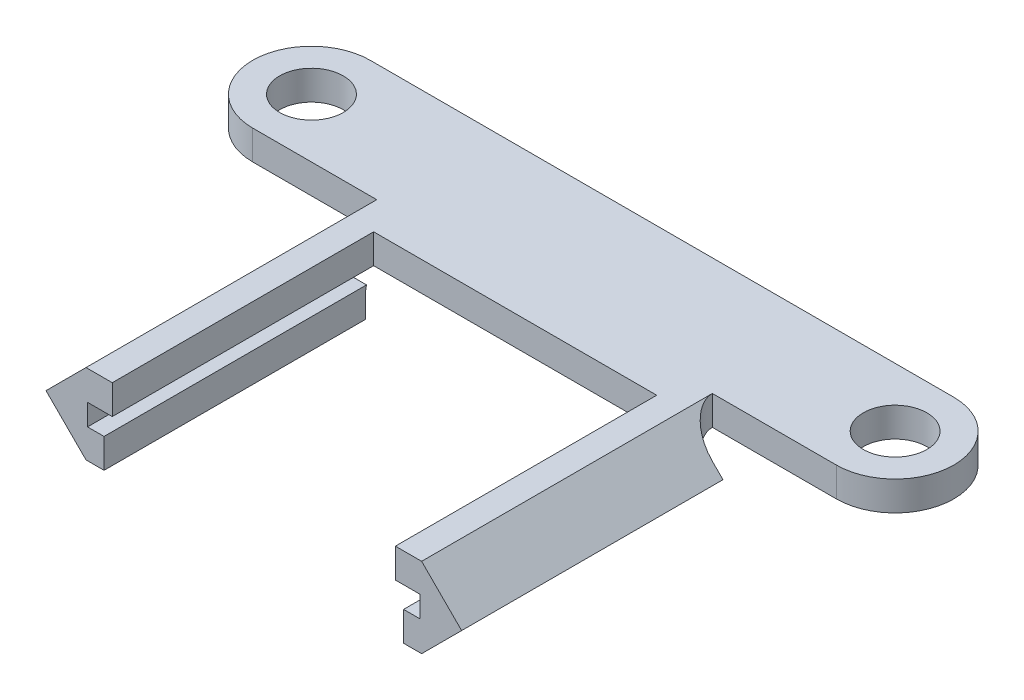
SolidWorks part; units mm, degrees
ref_plane "Front Plane" through (0, 0, 0) normal (0, 0, 1) x (1, 0, 0)
ref_plane "Top Plane" through (0, 0, 0) normal (0, 1, 0) x (1, 0, 0)
ref_plane "Right Plane" through (0, 0, 0) normal (1, 0, 0) x (0, 0, -1)
sketch "Sketch1" plane through (0, 0, 0) normal (0, 0, 1) x (1, 0, 0)
  line L0 (0.8255, 1.8415) -> (0, 1.8415)
  line L1 (0, 0) -> (0.8255, 0) construction
  line L2 (0, 0) -> (0, 1.8415) construction
  line L3 (0, 1.8415) -> (0.8255, 1.8415) construction
  line L4 (0.8255, 0) -> (0.8255, 1.8415) construction
  line L5 (0.4127, 1.8415) -> (0.4128, 0) construction
  line L6 (0, 0.9207) -> (0.8255, 0.9207) construction
  line L7 (0.8255, 0) -> (0, 0)
  line L8 (0, 0) -> (-0.9208, 0.9208) construction
  line L9 (-0.9208, 0.9208) -> (0, 1.8415) construction
  line L10 (26.0985, 0) -> (26.924, 0)
  line L11 (0.8255, 1.8415) -> (26.0985, 1.8415)
  line L12 (0.8255, 1.8415) -> (0.8255, 0) construction
  line L13 (0.8255, 0) -> (26.0985, 0)
  line L14 (26.0985, 1.8415) -> (26.0985, 0) construction
  line L15 (13.462, 0) -> (13.462, 1.8415) construction
  line L16 (0.8255, 0.9207) -> (26.0985, 0.9207) construction
  line L17 (26.924, 0) -> (27.8448, 0.9208) construction
  line L18 (26.0985, 1.8415) -> (26.924, 1.8415)
  line L19 (27.8448, 0.9208) -> (26.924, 1.8415) construction
  line L20 (-4.5129, 0.9207) -> (-1.0521, 4.3815)
  line L21 (0.8255, 4.3815) -> (-1.0521, 4.3815)
  line L22 (0.8255, 4.3815) -> (26.0985, 4.3815)
  line L23 (26.0985, 4.3815) -> (27.9761, 4.3815)
  line L24 (31.4369, 0.9207) -> (27.9761, 4.3815)
  line L25 (27.9761, -2.54) -> (31.4369, 0.9207)
  line L26 (26.0985, -2.54) -> (27.9761, -2.54)
  line L27 (0.8255, -2.54) -> (26.0985, -2.54)
  line L28 (0.8255, -2.54) -> (-1.0521, -2.54)
  line L29 (-1.0521, -2.54) -> (-4.5129, 0.9207)
  line L30 (0, 1.8415) -> (-0.9208, 1.8415)
  line L31 (-0.9208, 1.8415) -> (-0.9208, 0)
  line L32 (-0.9208, 0) -> (0, 0)
  line L33 (26.924, 1.8415) -> (27.8448, 1.8415)
  line L34 (27.8448, 1.8415) -> (27.8448, 0)
  line L35 (27.8448, 0) -> (26.924, 0)
  point P287 (13.462, 0.9207)
  point P500 (0.4127, 0.9207)
  dimension "D1" = 1.8415
  dimension "D2" = 0.8255
  dimension "D3" = 45
  dimension "D4" = 25.273
  dimension "D5" = 2.54
extrude "Boss-Extrude1" add sketch "Sketch1" along normal blind 22.606
sketch "Sketch2" plane through (0, 0, 22.606) normal (0, 0, 1) x (1, 0, 0)
  line L5 (13.462, 0) -> (13.462, -2.54) construction
  line L6 (-0.9208, 0) -> (27.8448, 0) construction
  line L7 (-1.0521, -2.54) -> (27.9761, -2.54) construction
  line L9 (0.508, 0) -> (26.416, 0)
  line L10 (0.508, 0) -> (0.508, -2.54)
  line L11 (0.508, -2.54) -> (26.416, -2.54)
  line L12 (26.416, 0) -> (26.416, -2.54)
  line L13 (13.462, -2.54) -> (13.462, 0) construction
  line L14 (0.508, -1.27) -> (26.416, -1.27) construction
  point P218 (13.462, -1.27)
  dimension "D1" = 0.508
extrude "Cut-Extrude1" cut sketch "Sketch2" against normal blind 22.606
sketch "Sketch5" plane through (0, 0, 0) normal (0, 0, -1) x (-1, 0, 0)
  line L12 (-31.4369, 0.9207) -> (-27.8448, 0.9208)
  line L13 (-27.8448, 0.9208) -> (-27.8448, 1.8415)
  line L14 (-27.8448, 1.8415) -> (0.9208, 1.8415)
  line L15 (0.9208, 1.8415) -> (0.9208, 0.9207)
  line L16 (0.9208, 1.8415) -> (0.9208, 0) construction
  line L17 (0.9208, 0.9207) -> (4.5129, 0.9207)
  line L18 (4.5129, 0.9207) -> (1.0521, 4.3815)
  line L19 (1.0521, 4.3815) -> (-27.9761, 4.3815)
  line L20 (-27.9761, 4.3815) -> (-31.4369, 0.9207)
extrude "Boss-Extrude2" add sketch "Sketch5" along normal blind 12.7
sketch "Sketch3" plane through (0, 4.3815, 0) normal (0, 1, 0) x (1, 0, 0)
  line L0 (13.462, 0) -> (13.462, -22.606) construction
  line L1 (27.9761, 0) -> (-1.0521, 0) construction
  line L2 (27.9761, -22.606) -> (-1.0521, -22.606) construction
  line L3 (6.1658, -15.0622) -> (3.048, -15.0622) construction
  line L4 (1.2192, 0) -> (25.7048, 0) construction
  line L5 (1.2192, 0) -> (1.2192, -22.606) construction
  line L6 (1.2192, -22.606) -> (25.7048, -22.606) construction
  line L7 (25.7048, 0) -> (25.7048, -22.606) construction
  line L8 (13.462, -22.606) -> (13.462, 0) construction
  line L9 (1.2192, -11.303) -> (25.7048, -11.303) construction
  line L10 (6.1658, 0) -> (20.7582, 0) construction
  line L11 (6.1658, 0) -> (6.1658, -15.0622) construction
  line L12 (6.1658, -15.0622) -> (20.7582, -15.0622) construction
  line L13 (20.7582, 0) -> (20.7582, -15.0622) construction
  line L14 (13.462, -15.0622) -> (13.462, 0) construction
  line L15 (6.1658, -7.5311) -> (20.7582, -7.5311) construction
  line L16 (3.048, 0) -> (23.876, 0) construction
  line L17 (3.048, 0) -> (3.048, -22.606) construction
  line L18 (3.048, -22.606) -> (23.876, -22.606) construction
  line L19 (23.876, 0) -> (23.876, -22.606) construction
  line L20 (13.462, -22.606) -> (13.462, 0) construction
  line L21 (3.048, -11.303) -> (23.876, -11.303) construction
  line L22 (3.048, -15.0622) -> (3.048, 0) construction
  line L23 (3.048, 0) -> (1.2192, 0)
  line L24 (1.2192, 0) -> (1.2192, -22.606)
  line L25 (1.2192, -22.606) -> (25.7048, -22.606)
  line L26 (25.7048, -22.606) -> (25.7048, 0)
  line L27 (25.7048, 0) -> (23.876, 0)
  line L28 (23.876, 0) -> (23.876, -15.0622) construction
  line L29 (23.876, -15.0622) -> (20.7582, -15.0622) construction
  line L32 (6.1658, 0) -> (20.7582, 0)
  line L33 (3.048, 0) -> (6.1658, 0)
  line L34 (20.7582, 0) -> (23.876, 0)
  point P250 (13.462, -11.303)
  point P383 (13.462, -7.5311)
  point P386 (13.462, -11.303)
  dimension "D1" = 24.4856
  dimension "D2" = 14.5923
  dimension "D3" = 15.0622
  dimension "D4" = 20.828
extrude "Cut-Extrude4" cut sketch "Sketch3" against normal up to vertex (2.54 mm away)
sketch "Sketch6" plane through (0, 0, -12.7) normal (0, 0, -1) x (-1, 0, 0)
  line L2 (-27.9761, 4.3815) -> (-31.4369, 0.9207)
  line L3 (-31.4369, 0.9207) -> (-27.8448, 0.9208)
  line L4 (-27.8448, 0.9208) -> (-27.8448, 1.8415)
  line L5 (-27.8448, 1.8415) -> (-27.9761, 1.8415)
  line L6 (-27.9761, 1.8415) -> (-27.9761, 4.3815)
  line L8 (-13.462, 4.3815) -> (-13.462, 1.8415) construction
  line L9 (-0.8255, 4.3815) -> (-26.0985, 4.3815) construction
  line L11 (1.0521, 1.8415) -> (1.0521, 4.3815)
  line L12 (0.9208, 1.8415) -> (1.0521, 1.8415)
  line L13 (0.9208, 0.9208) -> (0.9208, 1.8415)
  line L14 (4.5129, 0.9208) -> (0.9208, 0.9208)
  line L15 (1.0521, 4.3815) -> (4.5129, 0.9208)
extrude "Cut-Extrude5" cut sketch "Sketch6" against normal up to surface (12.7 mm away) up to face at (-1.0651, -0.5398, 0)
fillet "Fillet1" radius 2.54 8 edges at (27.9761, 3.1115, 0) (27.9104, 1.8415, 0) (-0.9864, 1.8415, 0) (-1.0521, 3.1115, 0) (-0.2064, 0, 0) (27.8448, 0.9207, 0) (27.1304, 0, 0) (-0.9208, 0.9208, 0)
sketch "Sketch7" plane through (0, 1.8415, 0) normal (0, -1, 0) x (1, 0, 0)
  line L2 (13.462, 0) -> (13.462, -12.7) construction
  line L3 (25.7048, 0) -> (1.2192, 0) construction
  line L4 (27.9761, -12.7) -> (-1.0521, -12.7) construction
  line L5 (-1.0521, -7.62) -> (27.9761, -7.62) construction
  line L6 (-1.0521, -2.54) -> (-1.0521, -12.7) construction
  line L7 (27.9761, -2.54) -> (27.9761, -12.7) construction
  line L8 (-1.0521, -7.62) -> (-11.778, -7.62) construction
  line L9 (-1.0521, -2.54) -> (-11.778, -2.54)
  line L10 (-1.0521, -2.54) -> (27.9761, -2.54)
  line L11 (27.9761, -2.54) -> (38.702, -2.54)
  line L12 (27.9761, -12.7) -> (38.702, -12.7)
  line L13 (-1.0521, -12.7) -> (27.9761, -12.7)
  line L14 (-1.0521, -12.7) -> (-11.778, -12.7)
  line L15 (-11.778, -2.54) -> (-11.778, -12.7) construction
  circle A4 centre (-11.778, -7.62) radius 2 construction
  circle A5 centre (38.702, -7.62) radius 2 construction
  arc A6 (-11.778, -12.7) -> (-11.778, -2.54) centre (-11.778, -7.62) cw
  arc A7 (38.702, -12.7) -> (38.702, -2.54) centre (38.702, -7.62) ccw
  dimension "D1" = 50.48
  dimension "D2" = 4
extrude "Boss-Extrude3" add sketch "Sketch7" against normal up to surface (2.54 mm away) up to face at (13.462, 4.3815, 5.9944)
hole_wizard "M5 Clearance Hole1" positions "Sketch8" profile "Sketch9" hole size "M5" standard "ANSI Metric" end condition through all
sketch "Sketch8" plane through (0, 1.8415, 0) normal (0, -1, 0) x (-1, 0, 0)
  point P6 (-38.702, 7.62)
  point P10 (11.778, 7.62)
sketch "Sketch9" plane through (38.702, 1.8415, -7.62) normal (1, 0, 0) x (0, 0, -1)
  line L0 (0, 0) -> (0, 2.54)
  line L1 (0, 2.54) -> (2.75, 2.54)
  line L2 (2.75, 2.54) -> (2.75, 0)
  line L5 (2.75, 0) -> (0, 0)
  line L11 (0, -6.35) -> (0, 107.95) construction
  dimension "Thru Hole Dia." = 5.5
  dimension "Thru Hole Depth" = 2.54
